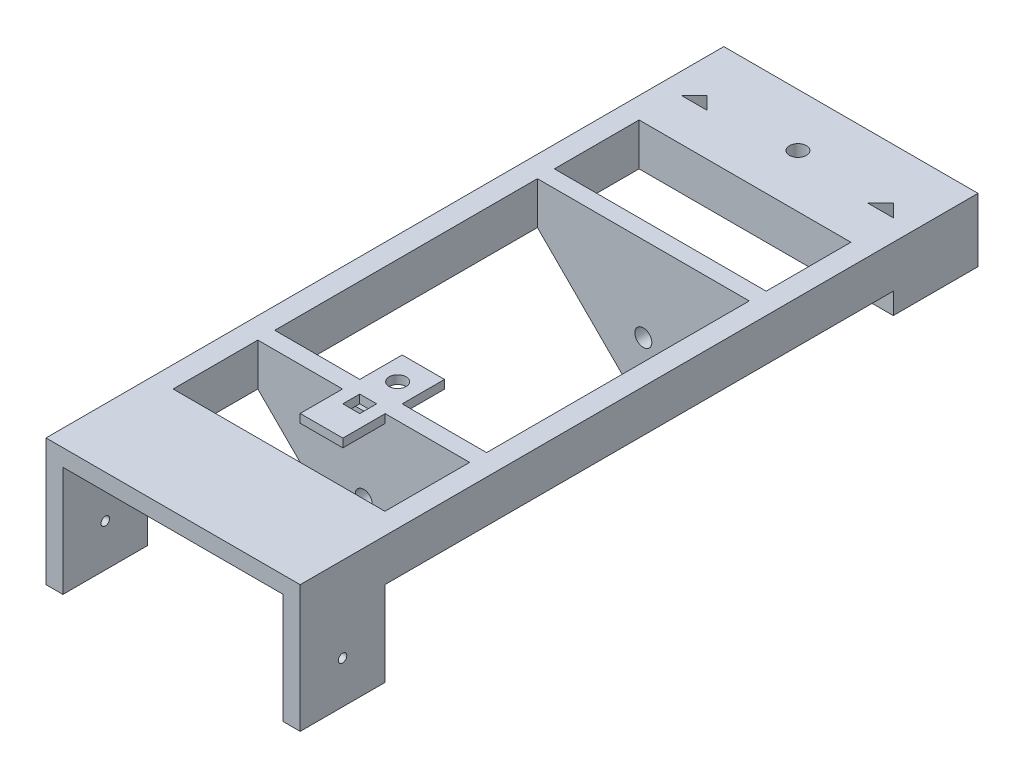
SolidWorks part; units mm, degrees
other "Markup1"
sketch "Sketch19" plane through (-15, 15, -40) normal (-0.0389, 0.0826, -0.9958) x (-0.519, -0.8533, -0.0505)
ref_plane "Front Plane" through (0, 0, 0) normal (0, 0, 1) x (1, 0, 0)
ref_plane "Top Plane" through (0, 0, 0) normal (0, 1, 0) x (1, 0, 0)
ref_plane "Right Plane" through (0, 0, 0) normal (1, 0, 0) x (0, 0, -1)
sketch "Sketch1" plane through (0, 0, 0) normal (0, 1, 0) x (1, 0, 0)
  line L1 (-15, 40) -> (15, 40)
  line L2 (-15, 40) -> (-15, -40)
  line L3 (-15, -40) -> (15, -40)
  line L4 (15, 40) -> (15, -40)
  line L5 (-15, 40) -> (15, -40) construction
  line L6 (-15, -40) -> (15, 40) construction
  point P0 (0, 0)
  dimension "D1" = 30
  dimension "D2" = 80
extrude "Boss-Extrude1" add sketch "Sketch1" along normal blind 5
sketch "Sketch2" plane through (15, 0, 0) normal (1, 0, 0) x (0, 0, -1)
  line L1 (-40, 0) -> (-30, 0)
  line L2 (-40, 0) -> (-40, -10)
  line L3 (-40, -10) -> (-30, -10)
  line L4 (-30, 0) -> (-30, -10)
  line L5 (40, 0) -> (30, 0)
  line L6 (40, 0) -> (40, -10)
  line L7 (40, -10) -> (30, -10)
  line L8 (30, 0) -> (30, -10)
  dimension "D1" = 10
  dimension "D2" = 10
  dimension "D3" = 10
  dimension "D4" = 10
extrude "Boss-Extrude2" add sketch "Sketch2" against normal blind 30
sketch "Sketch3" plane through (15, 0, 0) normal (1, 0, 0) x (0, 0, -1)
  line L0 (-40, 5) -> (-40, -10) construction
  line L2 (-40, -10) -> (-30, -10) construction
  line L15 (40, 5) -> (40, -10) construction
  line L16 (30, -10) -> (40, -10)
  line L17 (30, -10) -> (30, -2.5)
  line L18 (30, -2.5) -> (40, -2.5)
  line L19 (40, -10) -> (40, -2.5)
  circle A0 centre (-35, -5) radius 0.5
  dimension "D1" = 1
  dimension "D2" = 7.5
  dimension "D3" = 5
  dimension "D4" = 5
extrude "Cut-Extrude1" cut sketch "Sketch3" against normal through all both and the other way through all
sketch "Sketch4" plane through (0, 5, 0) normal (0, 1, 0) x (1, 0, 0)
  line L9 (-12.5, -27.5) -> (12.5, -27.5)
  line L10 (-12.5, -27.5) -> (-12.5, 27.5)
  line L11 (-12.5, 27.5) -> (12.5, 27.5)
  line L12 (12.5, -27.5) -> (12.5, 27.5)
  line L13 (-12.5, -27.5) -> (12.5, 27.5) construction
  line L14 (-12.5, 27.5) -> (12.5, -27.5) construction
  point P0 (0, 0)
  dimension "D1" = 55
  dimension "D2" = 25
extrude "Cut-Extrude2" cut sketch "Sketch4" against normal through all both and the other way through all
sketch "Sketch20" plane through (0, 5, 0) normal (0, 1, 0) x (1, 0, 0)
  line L0 (11, 34) -> (9.5, 32.5)
  line L1 (11, 34) -> (12.5, 32.5)
  line L2 (9.5, 32.5) -> (12.5, 32.5)
  line L3 (-11, 34) -> (-12.5, 32.5)
  line L4 (-11, 34) -> (-9.5, 32.5)
  line L5 (-12.5, 32.5) -> (-9.5, 32.5)
  line L6 (-15, 40) -> (-15, -40) construction
  line L7 (15, -40) -> (15, 40) construction
  line L9 (12.5, 27.5) -> (-12.5, 27.5) construction
  dimension "D1" = 3
  dimension "D2" = 3
  dimension "D3" = 5
  dimension "D4" = 5
  dimension "D5" = 2.5
  dimension "D6" = 2.5
extrude "Cut-Extrude4" cut sketch "Sketch20" against normal through all both and the other way through all
sketch "Sketch21" plane through (0, 5, 0) normal (0, 1, 0) x (1, 0, 0)
  line L0 (12.5, 27.5) -> (-12.5, 27.5) construction
  line L1 (-15, 40) -> (-15, -40) construction
  circle A0 centre (0, 33.75) radius 1
  dimension "D1" = 2
  dimension "D2" = 6.25
  dimension "D3" = 15
extrude "Cut-Extrude5" cut sketch "Sketch21" against normal through all both and the other way through all
sketch "Sketch22" plane through (0, 0, 40) normal (0, 0, 1) x (1, 0, 0)
  line L0 (-15, -10) -> (15, -10) construction
  line L1 (-13, -10) -> (13, -10)
  line L2 (-13, -10) -> (-13, 3)
  line L3 (-13, 3) -> (13, 3)
  line L4 (13, -10) -> (13, 3)
  line L5 (-15, 5) -> (15, 5) construction
  line L6 (-15, 5) -> (-15, -10) construction
  line L7 (15, 5) -> (15, -10) construction
  dimension "D1" = 2
  dimension "D2" = 2
  dimension "D3" = 2
extrude "Cut-Extrude6" cut sketch "Sketch22" against normal up to surface (10 mm away) up to face at (0, -5, 30)
sketch "Sketch23" plane through (0, 5, 0) normal (0, 1, 0) x (1, 0, 0)
  line L0 (-12.5, 27.5) -> (-12.5, -27.5) construction
  line L1 (-12.5, 15.5) -> (12.5, 15.5)
  line L2 (-12.5, 15.5) -> (-12.5, 17.5)
  line L3 (-12.5, 17.5) -> (12.5, 17.5)
  line L4 (12.5, 15.5) -> (12.5, 17.5)
  line L5 (12.5, -27.5) -> (12.5, 27.5) construction
  line L6 (12.5, 27.5) -> (-12.5, 27.5) construction
  line L7 (-12.5, -17.5) -> (12.5, -17.5)
  line L8 (-12.5, -17.5) -> (-12.5, -15.5)
  line L9 (-12.5, -15.5) -> (12.5, -15.5)
  line L10 (12.5, -17.5) -> (12.5, -15.5)
  line L11 (-12.5, -27.5) -> (12.5, -27.5) construction
  dimension "D1" = 2
  dimension "D2" = 2
  dimension "D3" = 10
  dimension "D4" = 10
extrude "Boss-Extrude3" add sketch "Sketch23" against normal blind 15
sketch "Sketch24" plane through (0, 0, 17.5) normal (0, 0, 1) x (1, 0, 0)
  line L0 (-12.5, -10) -> (12.5, -10) construction
  line L1 (-12.5, -10) -> (-12.5, 0) construction
  circle A0 centre (0, -5) radius 1
  dimension "D1" = 2
  dimension "D2" = 5
  dimension "D3" = 12.5
extrude "Cut-Extrude7" cut sketch "Sketch24" against normal up to surface (35 mm away) contours A0 up to face at (0, -1.6667, -17.5)
chamfer "Chamfer1" distance 10 angle 45 4 edges at (-12.5, -10, 16.5) (12.5, -10, 16.5) (-12.5, -10, -16.5) (12.5, -10, -16.5)
sketch "Sketch25" plane through (0, 5, 0) normal (0, 1, 0) x (1, 0, 0)
  line L5 (12.5, -15.5) -> (-12.5, -15.5) construction
  line L6 (-2.4635, -15.5) -> (2.5365, -15.5)
  line L7 (-2.4635, -15.5) -> (-2.4635, -10.5)
  line L8 (-2.4635, -10.5) -> (2.5365, -10.5)
  line L9 (2.5365, -15.5) -> (2.5365, -10.5)
  line L10 (-2.4635, -15.5) -> (2.5365, -10.5) construction
  line L11 (-2.4635, -10.5) -> (2.5365, -15.5) construction
  line L12 (-2.5, -17.5) -> (2.5365, -17.5)
  line L13 (-2.5, -17.5) -> (-2.5, -22.5)
  line L14 (-2.5, -22.5) -> (2.5365, -22.5)
  line L15 (2.5365, -17.5) -> (2.5365, -22.5)
  point P0 (0, 0)
  point P1 (0.0365, -13)
  dimension "D1" = 5
  dimension "D2" = 5
  dimension "D3" = 0
  dimension "D4" = 5
extrude "Boss-Extrude4" add sketch "Sketch25" against normal blind 1
sketch "Sketch26" plane through (0, 5, 0) normal (0, 1, 0) x (1, 0, 0)
  line L0 (-2.4635, -15.5) -> (-12.5, -15.5) construction
  circle A0 centre (0, -13.5) radius 1
  dimension "D1" = 2
  dimension "D2" = 2
extrude "Cut-Extrude8" cut sketch "Sketch26" against normal through all both and the other way through all
sketch "Sketch27" plane through (0, 5, 0) normal (0, 1, 0) x (1, 0, 0)
  line L1 (-0.9711, -19) -> (1.0289, -19)
  line L2 (-0.9711, -19) -> (-0.9711, -17)
  line L3 (-0.9711, -17) -> (1.0289, -17)
  line L4 (1.0289, -19) -> (1.0289, -17)
  line L5 (-0.9711, -19) -> (1.0289, -17) construction
  line L6 (-0.9711, -17) -> (1.0289, -19) construction
  circle A0 centre (0, -13.5) radius 1 construction
  point P0 (0.0289, -18)
  dimension "D3" = 4.5
  dimension "D1" = 2
  dimension "D2" = 2
extrude "Cut-Extrude9" cut sketch "Sketch27" against normal blind 1
equation "\"w\"=3.9113"
